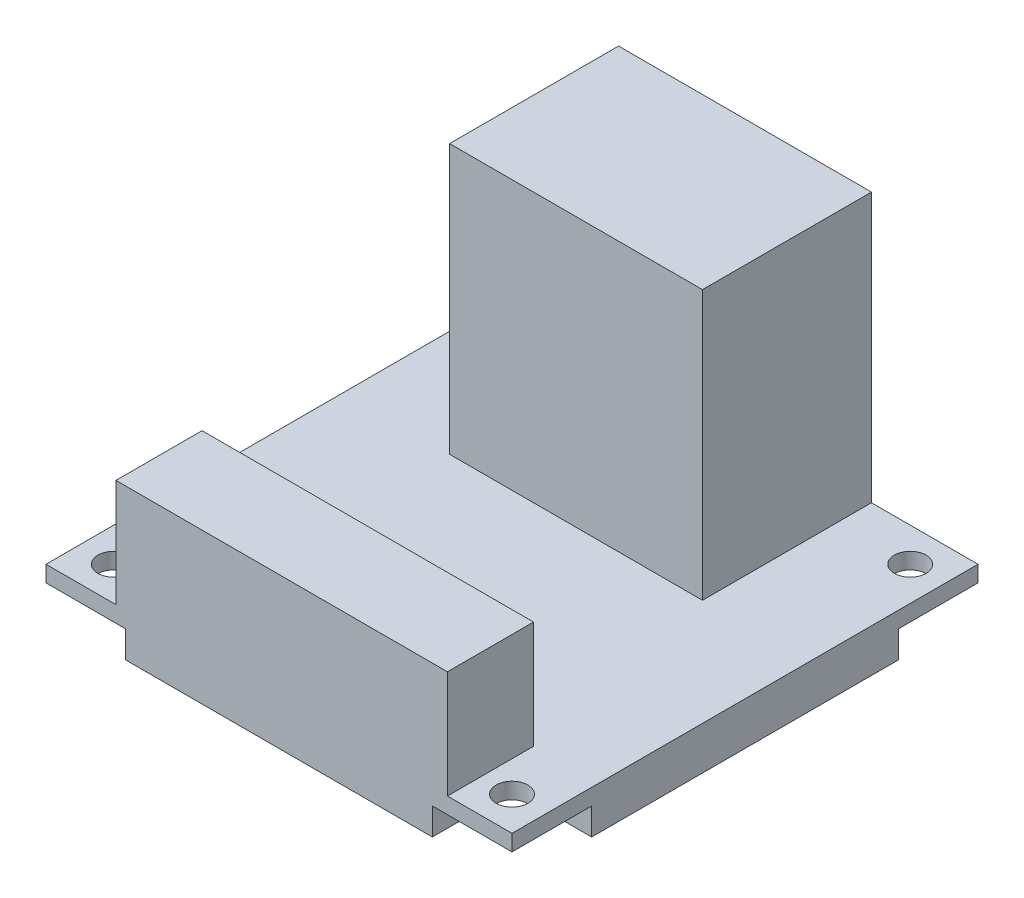
SolidWorks part; units mm, degrees
ref_plane "Front Plane" through (0, 0, 0) normal (0, 0, 1) x (1, 0, 0)
ref_plane "Top Plane" through (0, 0, 0) normal (0, 1, 0) x (1, 0, 0)
ref_plane "Right Plane" through (0, 0, 0) normal (1, 0, 0) x (0, 0, -1)
sketch "Sketch1" plane through (0, 0, 0) normal (0, 1, 0) x (1, 0, 0)
  line L0 (3.15, 38.675) -> (3.15, 4.625) construction
  line L1 (0, 0) -> (43.3, 0)
  line L2 (0, 0) -> (0, 43.3)
  line L3 (0, 43.3) -> (43.3, 43.3)
  line L4 (43.3, 0) -> (43.3, 43.3)
  line L5 (4.625, 3.15) -> (38.675, 3.15) construction
  circle A0 centre (3.15, 3.15) radius 1.475
  circle A1 centre (3.15, 40.15) radius 1.475
  circle A2 centre (40.15, 40.15) radius 1.475
  circle A3 centre (40.15, 3.15) radius 1.475
  point P13 (21.65, 3.15)
  point P16 (21.65, 0)
  point P19 (3.15, 21.65)
  point P20 (0, 21.65)
  dimension "D2" = 2.95
  dimension "D1" = 43.3
  dimension "D3" = 34.05
extrude "Boss-Extrude1" add sketch "Sketch1" along normal blind 1.5
sketch "Sketch2" plane through (0, 0, 0) normal (0, -1, 0) x (1, 0, 0)
  line L0 (0, -35.9) -> (0, -7.4)
  line L1 (0, -43.3) -> (0, 0) construction
  line L2 (0, -7.4) -> (7.4, -7.4)
  line L3 (7.4, -7.4) -> (7.4, 0)
  line L4 (0, 0) -> (43.3, 0) construction
  line L5 (7.4, 0) -> (35.9, 0)
  line L6 (35.9, 0) -> (35.9, -7.4)
  line L7 (35.9, -7.4) -> (43.3, -7.4)
  line L8 (43.3, 0) -> (43.3, -43.3) construction
  line L9 (43.3, -7.4) -> (43.3, -35.9)
  line L10 (43.3, -35.9) -> (35.9, -35.9)
  line L11 (35.9, -35.9) -> (35.9, -43.3)
  line L12 (35.9, -43.3) -> (7.4, -43.3)
  line L13 (43.3, -43.3) -> (0, -43.3) construction
  line L14 (7.4, -43.3) -> (7.4, -35.9)
  line L15 (7.4, -35.9) -> (0, -35.9)
  point P14 (0, 0)
  point P21 (7.0476, -9.4341)
  point P22 (7.0476, -11.5762)
  dimension "D1" = 28.5
extrude "Boss-Extrude2" add sketch "Sketch2" along normal blind 2.5
sketch "Sketch3" plane through (0, 1.5, 0) normal (0, 1, 0) x (1, 0, 0)
  line L0 (0, 0) -> (43.3, 0) construction
  line L1 (6.5, 0) -> (37.3, 0)
  line L2 (6.5, 0) -> (6.5, 8)
  line L3 (6.5, 8) -> (37.3, 8)
  line L4 (37.3, 0) -> (37.3, 8)
  dimension "D1" = 6
  dimension "D2" = 6.5
  dimension "D3" = 8
extrude "Boss-Extrude3" add sketch "Sketch3" along normal blind 10
sketch "Sketch4" plane through (0, 1.5, 0) normal (0, 1, 0) x (1, 0, 0)
  line L0 (43.3, 43.3) -> (0, 43.3) construction
  line L1 (33.4, 43.3) -> (9.9, 43.3)
  line L2 (33.4, 43.3) -> (33.4, 27.6)
  line L3 (33.4, 27.6) -> (9.9, 27.6)
  line L4 (9.9, 43.3) -> (9.9, 27.6)
  dimension "D1" = 9.9
  dimension "D2" = 9.9
  dimension "D3" = 15.7
extrude "Boss-Extrude4" add sketch "Sketch4" along normal blind 25
